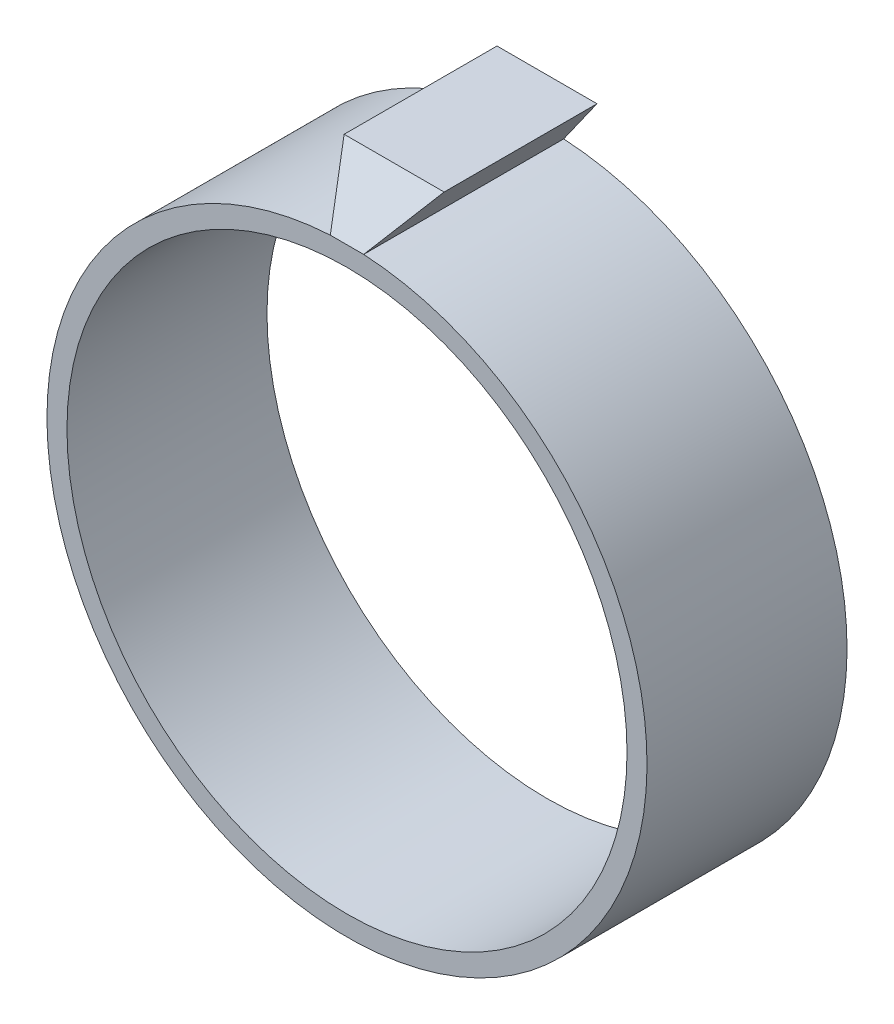
SolidWorks part; units mm, degrees
ref_plane "Front Plane" through (0, 0, 0) normal (0, 0, 1) x (1, 0, 0)
ref_plane "Top Plane" through (0, 0, 0) normal (0, 1, 0) x (1, 0, 0)
ref_plane "Right Plane" through (0, 0, 0) normal (1, 0, 0) x (0, 0, -1)
sketch "Sketch1" plane through (0, 0, 0) normal (0, 0, 1) x (1, 0, 0)
  line L0 (0, 42) -> (0, 52) construction
  line L3 (-7.5, 52) -> (7.5, 52)
  line L4 (-7.5, 52) -> (-2.5, 44.9305)
  line L5 (7.5, 52) -> (2.5, 44.9305)
  circle A0 centre (0, 0) radius 42
  arc A1 (-25, 33.7491) -> (25, 33.7491) centre (0, 0) cw
  arc A2 (26.7857, 36.1597) -> (-2.5, 44.9305) centre (0, 0) cw
  arc A3 (2.5, 44.9305) -> (26.7857, 36.1597) centre (0, 0) cw
  arc A4 (-26.7857, 36.1597) -> (26.7857, 36.1597) centre (0, 0) cw construction
  point P3 (-25, 33.7491)
  point P4 (25, 33.7491)
  point P16 (0, 52)
  point P18 (0, 47)
  dimension "D1" = 84
  dimension "D2" = 50
  dimension "D3" = 10
  dimension "D5" = 15
  dimension "D6" = 2.5
  dimension "D4" = 3
extrude "Boss-Extrude1" add sketch "Sketch1" along normal blind 30 contours A3 L5 L3 L4 A2 A0 region at (0, 50.6768, 0)
sketch "Sketch3" plane through (0, 0, 0) normal (1, 0, 0) x (0, 0, -1)
  line L0 (-30, 44.9305) -> (-22.9305, 52)
  line L1 (-30, 52) -> (0, 52) construction
  line L5 (-22.9305, 52) -> (-30, 52)
  line L6 (-30, 52) -> (-30, 44.9305)
extrude "Cut-Extrude1" cut sketch "Sketch3" against normal up to surface and the other way up to surface up to face at (-5, 48.4653, 15) other way up to face at (5, 48.4653, 15)
